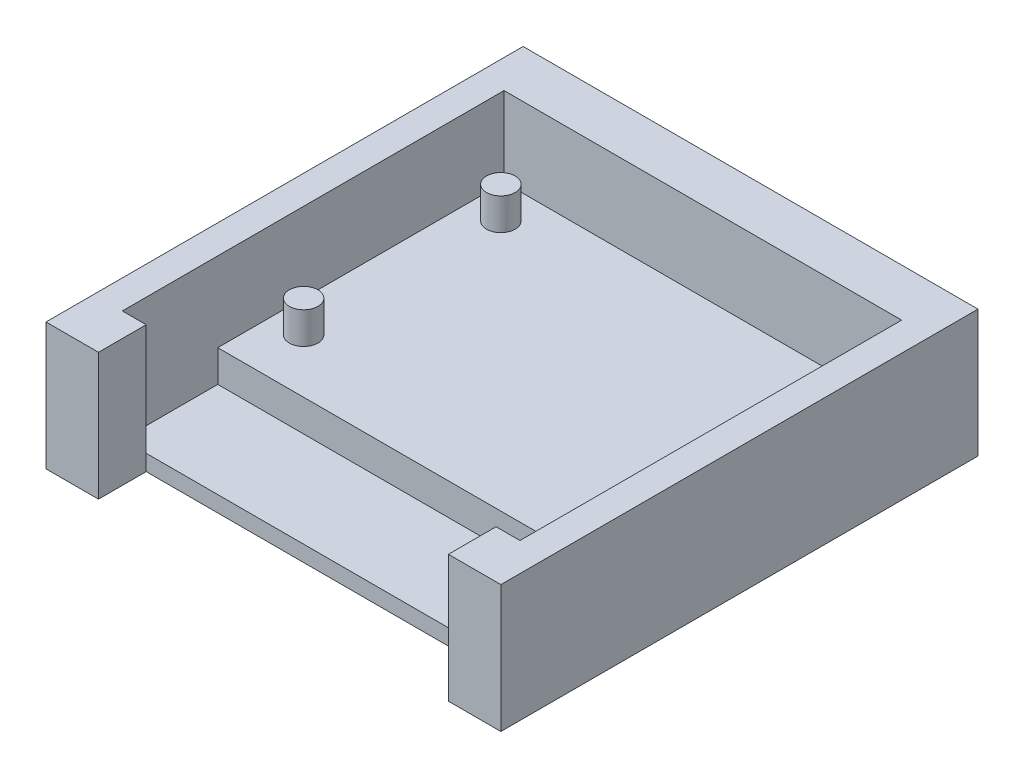
SolidWorks part; units mm, degrees
ref_plane "前视基准面" through (0, 0, 0) normal (0, 0, 1) x (1, 0, 0)
ref_plane "上视基准面" through (0, 0, 0) normal (0, 1, 0) x (1, 0, 0)
ref_plane "右视基准面" through (0, 0, 0) normal (1, 0, 0) x (0, 0, -1)
sketch "草图1" plane through (0, 0, 0) normal (0, 1, 0) x (1, 0, 0)
  line L0 (0, 4.8418) -> (0, -11.4873) construction
  line L1 (-12.5, 12) -> (12.5, 12)
  line L2 (-12.5, 12) -> (-12.5, -12)
  line L3 (-12.5, -12) -> (12.5, -12)
  line L4 (12.5, 12) -> (12.5, -12)
  line L5 (18.7975, 0) -> (-19.4304, 0) construction
  line L7 (-14.3, 15) -> (14.3, 15)
  line L8 (-14.3, 15) -> (-14.3, -15)
  line L9 (-14.3, -15) -> (14.3, -15)
  line L10 (14.3, 15) -> (14.3, -15)
  point P13 (0, 0)
  point P14 (0, 0)
  dimension "D1" = 25
  dimension "D2" = 24
  dimension "D3" = 1.8
  dimension "D4" = 1.8
  dimension "D5" = 3
  dimension "D6" = 3
extrude "凸台-拉伸1" add sketch "草图1" along normal blind 3 contours L10 L9 L8 L7
extrude "凸台-拉伸2" add sketch "草图1<4>" along normal blind 8
sketch "草图1<4>" plane through (0, 0, 0) normal (0, 1, 0) x (1, 0, 0) same geometry as "草图1"
ref_plane "基准面1" through (0, 8, 0) normal (0, 1, 0) x (1, 0, 0)
sketch "草图2" plane through (0, 8, 0) normal (0, 1, 0) x (1, 0, 0)
  line L0 (-14.3, -15) -> (14.3, -15) construction
  line L1 (-11, -12) -> (11, -12)
  line L2 (-11, -12) -> (-11, -15)
  line L3 (-11, -15) -> (11, -15)
  line L4 (11, -12) -> (11, -15)
  line L5 (0, 7.2368) -> (0, -3.7682) construction
  dimension "D1" = 22
  dimension "D2" = 3
extrude "切除-拉伸1" cut sketch "草图2" against normal blind 8
ref_plane "基准面2" through (0, 3, 0) normal (0, 1, 0) x (1, 0, 0)
sketch "草图3" plane through (0, 3, 0) normal (0, 1, 0) x (1, 0, 0)
  line L0 (12.5, 12) -> (-12.5, 12) construction
  line L1 (-12.5, -6) -> (12.5, -6)
  line L2 (-12.5, -6) -> (-12.5, -12)
  line L3 (-12.5, -12) -> (12.5, -12)
  line L4 (12.5, -6) -> (12.5, -12)
  line L5 (0, 6.2278) -> (0, -2.7907) construction
  line L6 (-11, -12) -> (11, -12) construction
  dimension "D1" = 6
extrude "切除-拉伸2" cut sketch "草图3" against normal blind 2
ref_plane "基准面3" through (0, 3, 0) normal (0, 1, 0) x (1, 0, 0)
sketch "草图4" plane through (0, 3, 0) normal (0, 1, 0) x (1, 0, 0)
  line L0 (0, 8.3405) -> (0, -4.3988) construction
  line L1 (12.5, 12) -> (-12.5, 12) construction
  circle A0 centre (-10.5, 9.8) radius 0.9
  circle A1 centre (-10.5, -2.6) radius 0.9
  circle A2 centre (10.5, 9.8) radius 0.9
  circle A3 centre (10.5, -2.6) radius 0.9
  point P9 (0, 0)
  point P12 (-10.5, 9.3495)
  dimension "D5" = 1.8
  dimension "D1" = 21
  dimension "D2" = 21
  dimension "D3" = 12.4
  dimension "D4" = 12.4
  dimension "D6" = 2.2
extrude "凸台-拉伸3" add sketch "草图4" along normal blind 2
